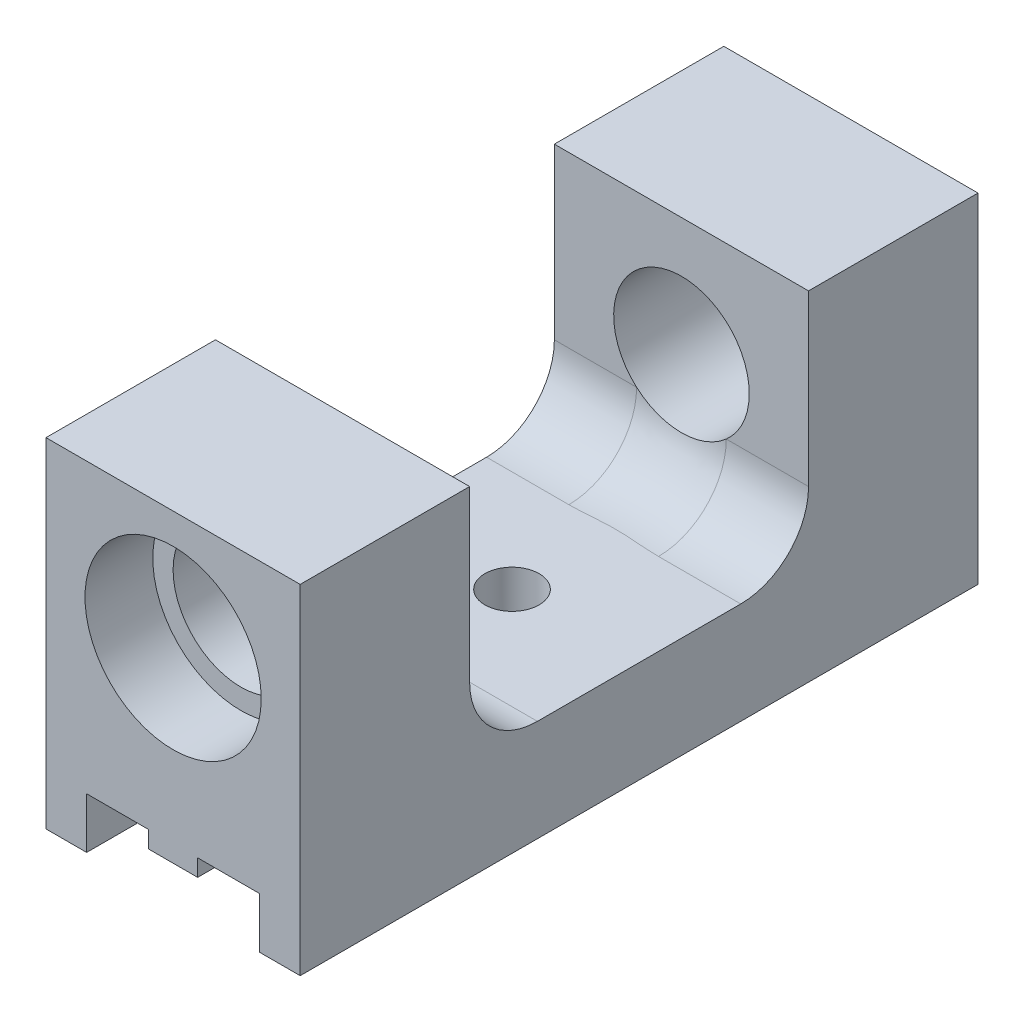
SolidWorks part; units mm, degrees
ref_plane "Front Plane" through (0, 0, 0) normal (0, 0, 1) x (1, 0, 0)
ref_plane "Top Plane" through (0, 0, 0) normal (0, 1, 0) x (1, 0, 0)
ref_plane "Right Plane" through (0, 0, 0) normal (1, 0, 0) x (0, 0, -1)
sketch "Sketch1" plane through (0, 0, 0) normal (0, 0, 1) x (1, 0, 0)
  line L0 (-5.1, 0) -> (-5.1, -3)
  line L1 (-5.1, 0) -> (-1.45, 0)
  line L2 (-1.45, 0) -> (-1.45, -1)
  line L3 (-1.45, -1) -> (1.45, -1)
  line L4 (1.45, -1) -> (1.45, 0)
  line L5 (1.45, 0) -> (5.1, 0)
  line L6 (5.1, 0) -> (5.1, -3)
  line L7 (7.5, 17) -> (-7.5, 17)
  line L8 (-5.1, -3) -> (-7.5, -3)
  line L9 (-7.5, -3) -> (-7.5, 17)
  line L10 (5.1, -3) -> (7.5, -3)
  line L11 (7.5, -3) -> (7.5, 17)
  point P0 (0, -1)
  dimension "D1" = 2.9
  dimension "D2" = 10.2
  dimension "D3" = 1
  dimension "D4" = 3
  dimension "D5" = 20
  dimension "D6" = 15
extrude "Main" add sketch "Sketch1" along normal mid plane 40
sketch "Sketch4" plane through (0, 17, 0) normal (0, 1, 0) x (1, 0, 0)
  circle A0 centre (0, 0) radius 1.6
  point P2 (0, 0)
  dimension "D1" = 3.2
extrude "FixHole" cut sketch "Sketch4" against normal through all
sketch "Sketch5" plane through (-7.5, 0, 0) normal (-1, 0, 0) x (0, 0, 1)
  line L0 (20, -3) -> (20, 17) construction
  line L1 (-10, 17) -> (10, 17)
  line L2 (-10, 17) -> (-10, 3)
  line L3 (-10, 3) -> (10, 3)
  line L4 (10, 17) -> (10, 3)
  line L5 (20, 17) -> (-20, 17) construction
  point P5 (0, 0)
  point P7 (0, 0)
  point P8 (0, 3)
  point P15 (-12, 17)
  dimension "D1" = 3
  dimension "D2" = 10
  dimension "D3" = 20
extrude "MiddleCut" cut sketch "Sketch5" against normal through all
sketch "Sketch6" plane through (0, 0, -20) normal (0, 0, 1) x (1, 0, 0)
  line L1 (1.45, 0) -> (5.1, 0) construction
  circle A0 centre (0, 10) radius 5.2
  point P2 (0, 0)
  point P4 (0, 0)
  point P7 (3.275, 0)
  dimension "D1" = 10.4
  dimension "D2" = 10
extrude "BearingHole" cut sketch "Sketch6" along normal blind 4 contours A0
mirror "MirrorBearingHole" about plane through (0, 0, 0) normal (0, 0, 1) of "BearingHole"
sketch "Sketch7" plane through (0, 0, 20) normal (0, 0, 1) x (1, 0, 0)
  circle A0 centre (0, 10) radius 4
  circle A1 centre (0, 10) radius 5.2 construction
  dimension "D1" = 8
extrude "Cut-Extrude6" cut sketch "Sketch7" against normal through all
fillet "Fillet1" radius 4 2 edges at (0, 3, -10) (0, 3, 10)
